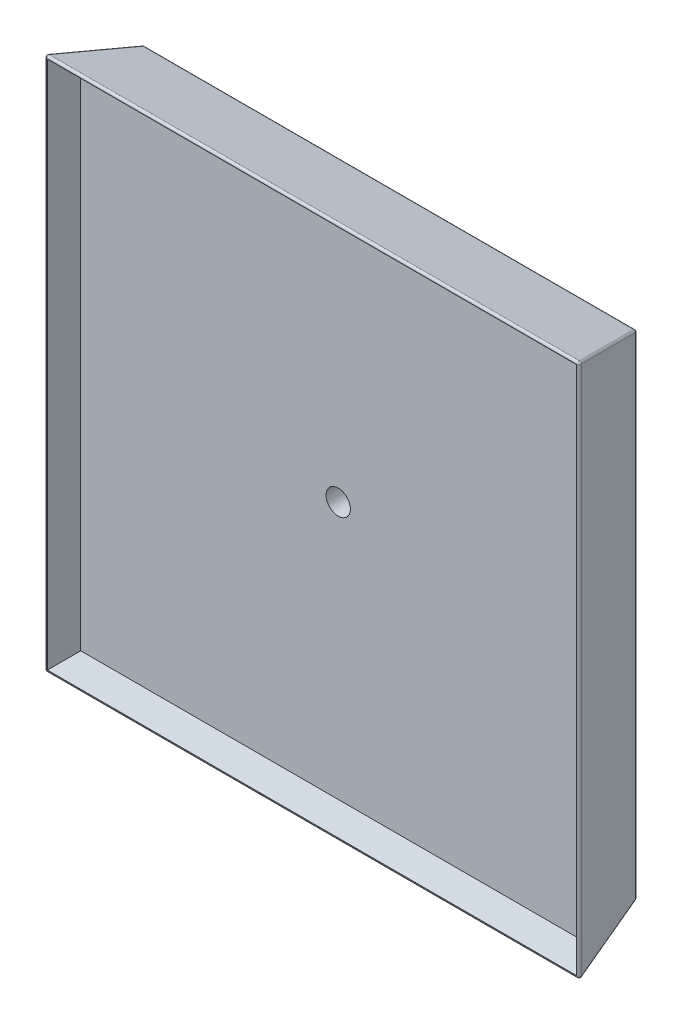
SolidWorks part; units mm, degrees
ref_plane "정면" through (0, 0, 0) normal (0, 0, 1) x (1, 0, 0)
ref_plane "윗면" through (0, 0, 0) normal (0, 1, 0) x (1, 0, 0)
ref_plane "우측면" through (0, 0, 0) normal (1, 0, 0) x (0, 0, -1)
sketch "스케치1" plane through (0, 0, 0) normal (0, 0, 1) x (1, 0, 0)
  line L1 (0, 0) -> (550, 0)
  line L2 (0, 0) -> (0, -550)
  line L3 (0, -550) -> (550, -550)
  line L4 (550, 0) -> (550, -550)
  dimension "D1" = 550
  dimension "D2" = 550
extrude "보스-돌출1" add sketch "스케치1" along normal blind 80 contours L1 L4 L3 L2
draft "구배3" type of draft neutral plane draft angle 15 faces to draft 4 face at (550, -275, 40) face at (275, -550, 40) face at (0, -275, 40) face at (275, 0, 40) neutral plane through (0, 0, 80) neutral plane normal (0, 0, 1) reverse direction yes parameters "D1"=15
fillet "필렛1" radius 2 12 edges at (0, -275, 80) (21.4359, -275, 0) (10.718, -539.282, 40) (275, -550, 80) (275, -528.5641, 0) (539.282, -539.282, 40) (550, -275, 80) (528.5641, -275, 0) (539.282, -10.718, 40) (275, 0, 80) (10.718, -10.718, 40) (275, -21.4359, 0)
shell "쉘8" thickness 3 removed face at (275, -275, 80)
ref_plane "평면1" through (0, 0, 53) normal (0, 0, 1) x (1, 0, 0)
sketch "스케치4" plane through (0, 0, 3) normal (0, 0, 1) x (1, 0, 0)
  line L0 (23.7379, -23.7379) -> (526.2621, -23.7379) construction
  line L1 (526.2621, -526.2621) -> (23.7379, -526.2621)
  line L2 (526.2621, -526.2621) -> (526.2621, -23.7379)
  line L3 (526.2621, -23.7379) -> (23.7379, -23.7379)
  line L4 (23.7379, -526.2621) -> (23.7379, -23.7379)
extrude "보스-돌출3" add sketch "스케치4" along normal blind 50 draft 15 separate body draft outward yes
sketch "스케치5" plane through (0, 0, 0) normal (0, 0, -1) x (-1, 0, 0)
  line L0 (-22.9706, -527.0294) -> (-22.9706, -22.9706) construction
  line L2 (-22.9706, -22.9706) -> (-527.0294, -22.9706) construction
  circle A0 centre (-274.9706, -274.9706) radius 12.5
  dimension "D3" = 25
  dimension "D1" = 252
  dimension "D2" = 252
extrude "컷-돌출1" cut sketch "스케치5" against normal through all both and the other way through all
